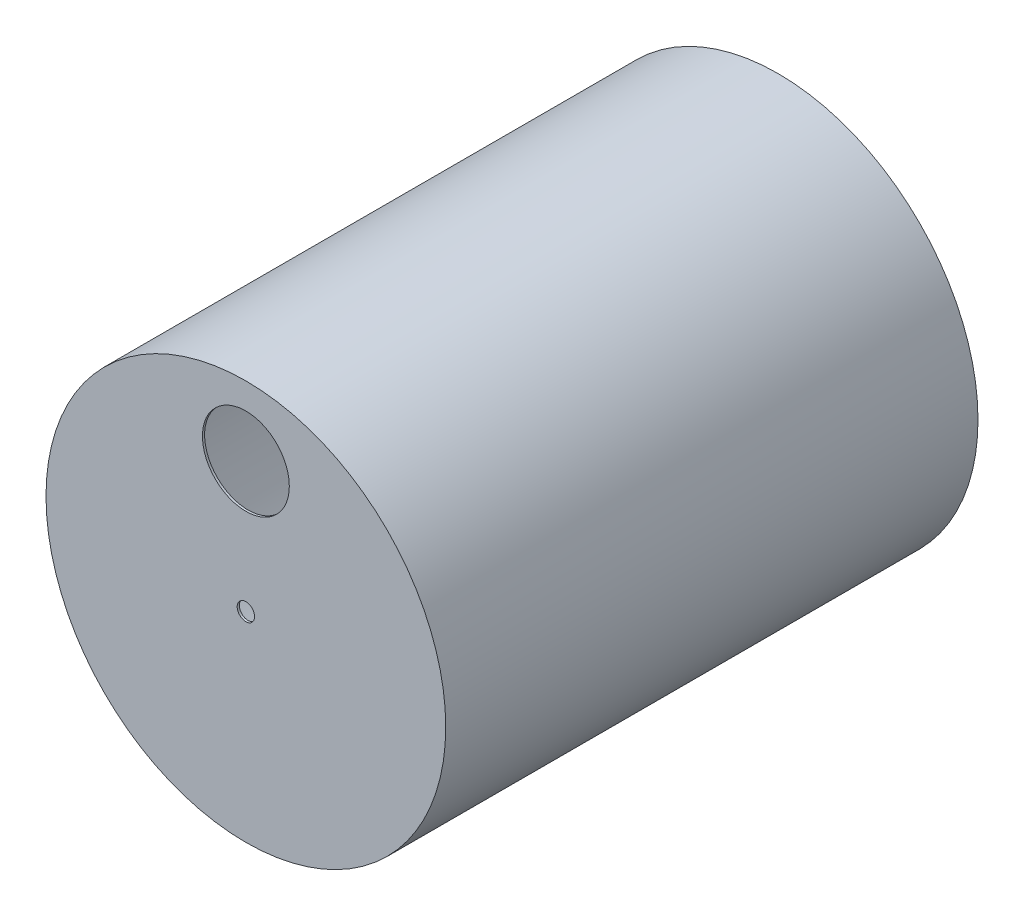
SolidWorks part; units mm, degrees
ref_plane "Front Plane" through (0, 0, 0) normal (0, 0, 1) x (1, 0, 0)
ref_plane "Top Plane" through (0, 0, 0) normal (0, 1, 0) x (1, 0, 0)
ref_plane "Right Plane" through (0, 0, 0) normal (1, 0, 0) x (0, 0, -1)
sketch "Sketch1" plane through (0, 0, 0) normal (0, 0, 1) x (1, 0, 0)
  circle A0 centre (0, 0) radius 92
  circle A1 centre (0, 0) radius 90
  dimension "D1" = 184
  dimension "D2" = 2
extrude "Boss-Extrude1" add sketch "Sketch1" along normal blind 245
sketch "Sketch2" plane through (0, 0, 245) normal (0, 0, 1) x (1, 0, 0)
  line L0 (0, 0) -> (0, 92) construction
  circle A0 centre (0, 0) radius 90
  circle A1 centre (0, 0) radius 4
  circle A2 centre (0, 0) radius 92 construction
  circle A3 centre (0, 60) radius 20
  dimension "D1" = 8
  dimension "D2" = 40
  dimension "D3" = 60
extrude "Boss-Extrude2" add sketch "Sketch2" against normal blind 1
